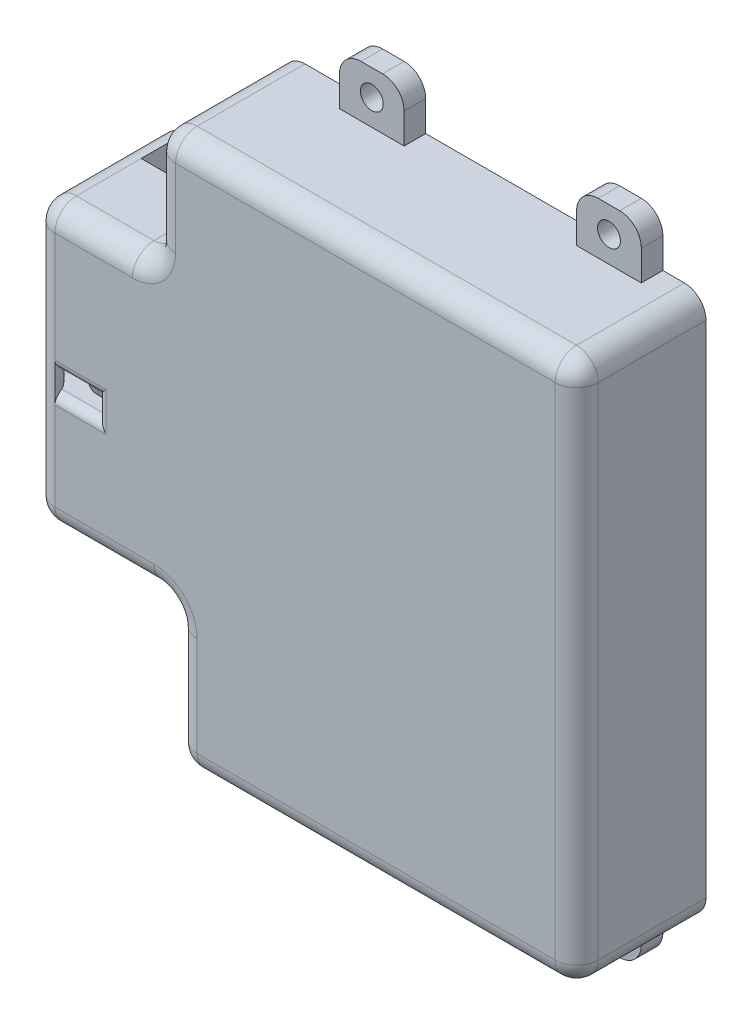
SolidWorks part; units mm, degrees
ref_plane "Plan de face" through (0, 0, 0) normal (0, 0, 1) x (1, 0, 0)
ref_plane "Plan de dessus" through (0, 0, 0) normal (0, 1, 0) x (1, 0, 0)
ref_plane "Plan de droite" through (0, 0, 0) normal (1, 0, 0) x (0, 0, -1)
sketch "Esquisse1" plane through (0, 0, 0) normal (0, 0, 1) x (1, 0, 0)
  line L0 (-58, 58) -> (-58, -58)
  line L1 (-55, 55) -> (55, 55) construction
  line L2 (-55, 55) -> (-55, -55) construction
  line L3 (-55, -55) -> (55, -55) construction
  line L4 (55, 55) -> (55, -55) construction
  line L5 (-55, 55) -> (55, -55) construction
  line L6 (-55, -55) -> (55, 55) construction
  line L7 (-58, -58) -> (58, -58)
  line L8 (58, 58) -> (58, -58)
  line L9 (-58, 58) -> (58, 58)
  line L10 (-63, -63) -> (63, -63)
  line L11 (63, 63) -> (63, -63)
  line L12 (-63, 63) -> (63, 63)
  line L13 (-63, 63) -> (-63, -63)
  point P0 (0, 0)
  dimension "D1" = 110
  dimension "D2" = 110
  dimension "D3" = 3
  dimension "D4" = 5
extrude "Boss.-Extru.1" add sketch "Esquisse1" along normal blind 25
sketch "Esquisse2" plane through (0, 0, 25) normal (0, 0, 1) x (1, 0, 0)
  line L1 (-63, 63) -> (63, 63)
  line L2 (-63, 63) -> (-63, -63)
  line L3 (-63, -63) -> (63, -63)
  line L4 (63, 63) -> (63, -63)
extrude "Boss.-Extru.2" add sketch "Esquisse2" along normal blind 5
sketch "Esquisse3" plane through (0, 0, 30) normal (0, 0, 1) x (1, 0, 0)
  line L0 (-63, 35) -> (-35, 35)
  line L1 (-55, 55) -> (55, 55) construction
  line L2 (-55, 55) -> (-55, -55) construction
  line L3 (-55, -55) -> (55, -55) construction
  line L4 (55, 55) -> (55, -55) construction
  line L5 (-55, 55) -> (55, -55) construction
  line L6 (-55, -55) -> (55, 55) construction
  line L7 (-63, 63) -> (-63, -63) construction
  line L8 (-35, 35) -> (-35, 63)
  line L9 (63, 63) -> (-63, 63) construction
  line L10 (-35, 63) -> (-63, 63)
  line L11 (-63, 63) -> (-63, 35)
  line L12 (-63, -30) -> (-30, -30)
  line L13 (-30, -30) -> (-30, -63)
  line L14 (-63, -63) -> (63, -63) construction
  line L15 (-30, -63) -> (-63, -63)
  line L16 (-63, -63) -> (-63, -30)
  point P0 (0, 0)
  dimension "D1" = 110
  dimension "D2" = 110
  dimension "D3" = 25
  dimension "D4" = 20
extrude "Enlèv. mat.-Extru.1" cut sketch "Esquisse3" against normal up to surface (30 mm away) up to face at (0, 0, 0)
sketch "Esquisse4" plane through (0, 0, 25) normal (0, 0, -1) x (-1, 0, 0)
  line L0 (35, 58) -> (35, 35)
  line L1 (35, 35) -> (58, 35)
  line L2 (58, 35) -> (58, -30) construction
  line L3 (58, 35) -> (35, 35) construction
  line L4 (58, 35) -> (58, 30)
  line L5 (58, 30) -> (30, 30)
  line L6 (30, 30) -> (30, 58)
  line L7 (-58, 58) -> (35, 58) construction
  line L8 (30, 58) -> (35, 58)
  line L9 (58, -25) -> (25, -25)
  line L10 (25, -25) -> (25, -58)
  line L11 (30, -58) -> (-58, -58) construction
  line L12 (25, -58) -> (30, -58)
  line L13 (30, -58) -> (30, -30)
  line L14 (30, -30) -> (58, -30)
  line L15 (58, -30) -> (58, -25)
  dimension "D1" = 5
  dimension "D2" = 5
  dimension "D3" = 5
  dimension "D4" = 5
extrude "Boss.-Extru.3" add sketch "Esquisse4" along normal blind 15
sketch "Esquisse5" plane through (0, 0, 0) normal (0, 0, 1) x (1, 0, 0)
  line L0 (-17, 63) -> (-17, 75)
  line L1 (63, 63) -> (-35, 63) construction
  line L2 (-17, 75) -> (-2, 75)
  line L3 (-2, 75) -> (-2, 63)
  line L4 (-2, 63) -> (-17, 63)
  line L5 (38, 63) -> (38, 75)
  line L6 (38, 75) -> (53, 75)
  line L7 (53, 75) -> (53, 63)
  line L8 (53, 63) -> (38, 63)
  line L9 (53, -63) -> (53, -75)
  line L10 (-30, -63) -> (63, -63) construction
  line L11 (53, -75) -> (38, -75)
  line L12 (38, -75) -> (38, -63)
  line L13 (-2, -63) -> (-2, -75)
  line L14 (-2, -75) -> (-17, -75)
  line L15 (-17, -75) -> (-17, -63)
  line L16 (-17, -63) -> (-2, -63)
  line L17 (38, -63) -> (53, -63)
  line L18 (63, -63) -> (63, 63) construction
  dimension "D1" = 10
  dimension "D2" = 15
  dimension "D3" = 40
  dimension "D4" = 15
  dimension "D5" = 10
  dimension "D6" = 15
  dimension "D7" = 40
  dimension "D8" = 15
  dimension "D9" = 12
  dimension "D10" = 12
  dimension "D11" = 12
  dimension "D12" = 12
extrude "Boss.-Extru.4" add sketch "Esquisse5" along normal blind 5
sketch "Esquisse6" plane through (0, 0, 5) normal (0, 0, 1) x (1, 0, 0)
  line L0 (-9.5, 75) -> (-9.5, 69) construction
  line L1 (-2, 75) -> (-17, 75) construction
  line L2 (45.5, 75) -> (45.5, 69) construction
  line L3 (53, 75) -> (38, 75) construction
  line L4 (-9.5, -75) -> (-9.5, -69) construction
  line L5 (-17, -75) -> (-2, -75) construction
  line L6 (45.5, -75) -> (45.5, -69) construction
  line L7 (38, -75) -> (53, -75) construction
  dimension "D1" = 6
  dimension "D2" = 6
  dimension "D3" = 6
  dimension "D4" = 6
fillet "Congé1" radius 5 40 edges at (-25, -41.5, 25) (16.5, -58, 25) (58, 0, 25) (14, 58, 25) (-30, 44, 25) (-44, 30, 25) (-58, 2.5, 25) (-41.5, -25, 25) (-63, 2.5, 30) (-49, 35, 30) (-35, 49, 30) (14, 63, 30) (63, 0, 30) (16.5, -63, 30) (-30, -46.5, 30) (-46.5, -30, 30) (58, -58, 12.5) (-25, -58, 17.5) (-25, -25, 17.5) (-58, -25, 17.5) (-58, 30, 17.5) (-30, 30, 17.5) (-30, 58, 17.5) (58, 58, 12.5) (53, -75, 2.5) (-2, -75, 2.5) (38, -75, 2.5) (-17, -75, 2.5) (-30, -63, 15) (-63, 35, 15) (-63, -30, 15) (-30, -30, 20) (-35, 35, 20) (53, 75, 2.5) (38, 75, 2.5) (-2, 75, 2.5) (-17, 75, 2.5) (63, 63, 15) (63, -63, 15) (-35, 63, 15)
chamfer "Chanfrein1" [suppressed] distance 20 angle 45
chamfer "Chanfrein2" [suppressed] distance 20 angle 45
hole_wizard "Dégagement M51" positions "Esquisse7" profile "Esquisse8" hole size "M5" standard "Ansi Metric" end condition through all
sketch "Esquisse7" plane through (0, 0, 0) normal (0, 0, 1) x (1, 0, 0)
  point P0 (-9.5, -69)
  point P3 (45.5, -69)
  point P6 (45.5, 69)
  point P9 (-9.5, 69)
  point P13 (45.5, -69)
  point P15 (-9.5, -69)
  point P17 (-9.5, 69)
  point P19 (45.5, 69)
sketch "Esquisse8" plane through (-9.5, -69, 0) normal (1, 0, 0) x (0, 1, 0)
  line L0 (0, 0) -> (0, 30)
  line L1 (0, 30) -> (2.65, 30)
  line L2 (2.65, 30) -> (2.65, 0)
  line L5 (2.65, 0) -> (0, 0)
  line L11 (0, -6.35) -> (0, 107.95) construction
  dimension "Diamètre du perçage jusqu'au prochain" = 5.3
  dimension "Profondeur du perçage jusqu'au prochain" = 30
sketch "Esquisse9" plane through (0, 0, 30) normal (0, 0, 1) x (1, 0, 0)
  line L1 (-48, 2.5) -> (-58, 2.5)
  line L2 (-48, 2.5) -> (-48, -2.5)
  line L3 (-48, -2.5) -> (-58, -2.5)
  line L4 (-58, 2.5) -> (-58, -2.5)
  line L5 (-48, 2.5) -> (-58, -2.5) construction
  line L6 (-48, -2.5) -> (-58, 2.5) construction
  line L8 (-58, 30) -> (-58, -25) construction
  point P0 (-53, 0)
  point P5 (48.38, 0)
  point P6 (54.9167, -10.6163)
  point P7 (58, 0)
  point P9 (-51.7277, 0)
  dimension "D1" = 5
  dimension "D2" = 10
  dimension "D3" = 0
  dimension "D4" = 0
ref_axis "Axe1" through (-63, 30, 30) along (0, -1, 0)
revolve "Enlèvement de matière-Révolution1" cut sketch "Esquisse9" angle 360 about axis through (-63, 30, 30) along (0, -1, 0)
fillet "Congé2" radius 2 6 edges at (-53, -2.5, 30) (-53, 2.5, 30) (-63, -2.5, 20) (-63, 2.5, 20) (-63, 0, 15) (-48, 0, 30)
